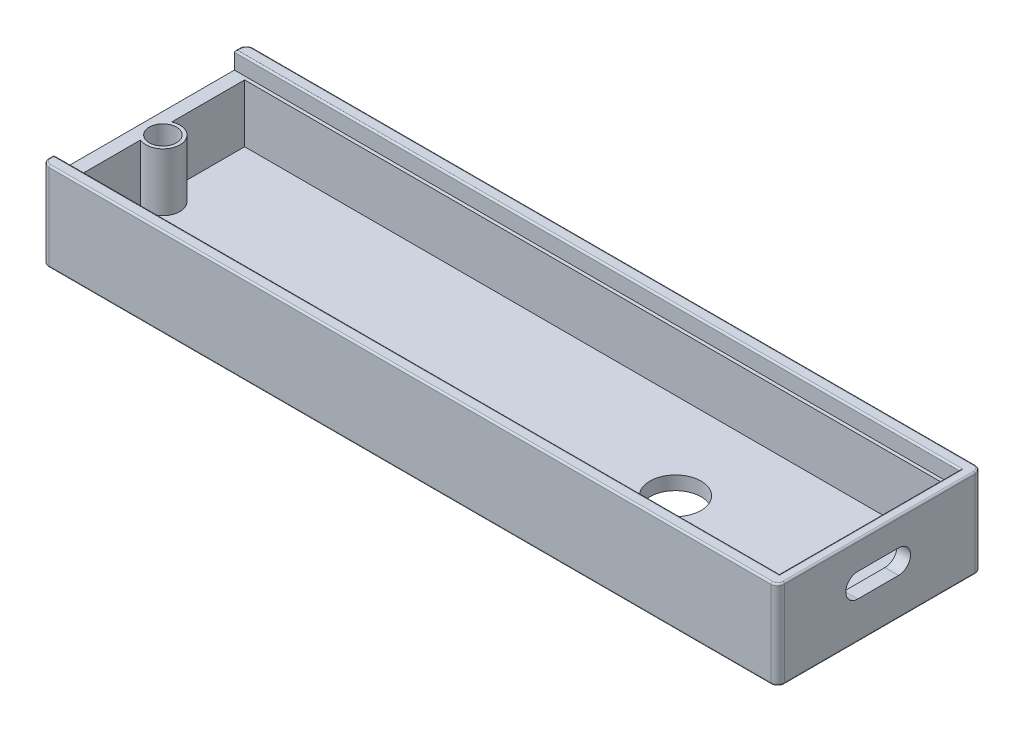
SolidWorks part; units mm, degrees
material "ABS"
ref_plane "Front Plane" through (0, 0, 0) normal (0, 0, 1) x (1, 0, 0)
ref_plane "Top Plane" through (0, 0, 0) normal (0, 1, 0) x (1, 0, 0)
ref_plane "Right Plane" through (0, 0, 0) normal (1, 0, 0) x (0, 0, -1)
sketch "Sketch1" plane through (0, 0, 0) normal (0, 1, 0) x (1, 0, 0)
  line L1 (0, 0) -> (108, 0)
  line L2 (0, 0) -> (0, -30)
  line L3 (0, -30) -> (108, -30)
  line L4 (108, 0) -> (108, -30)
  dimension "D1" = 108
  dimension "D2" = 30
extrude "Boss-Extrude1" add sketch "Sketch1" against normal blind 13
sketch "Sketch2" plane through (0, 0, 0) normal (0, 1, 0) x (1, 0, 0)
  line L0 (0, -30) -> (108, -30) construction
  line L1 (0, -1.75) -> (106.5, -1.75)
  line L2 (0, -1.75) -> (0, -28.25)
  line L3 (0, -28.25) -> (106.5, -28.25)
  line L4 (106.5, -1.75) -> (106.5, -28.25)
  line L6 (108, -30) -> (108, 0) construction
  line L8 (0, 0) -> (0, -30) construction
  line L10 (108, 0) -> (0, 0) construction
  dimension "D1" = 1.75
  dimension "D2" = 1.75
  dimension "D3" = 1.5
extrude "Cut-Extrude1" cut sketch "Sketch2" against normal blind 2.5
sketch "Sketch3" plane through (0, 0, 0) normal (0, 1, 0) x (1, 0, 0)
  line L0 (106.5, -1.75) -> (0, -1.75) construction
  line L1 (2, -2.25) -> (106, -2.25)
  line L2 (2, -2.25) -> (2, -27.75)
  line L3 (2, -27.75) -> (106, -27.75)
  line L4 (106, -2.25) -> (106, -27.75)
  line L5 (106.5, -28.25) -> (106.5, -1.75) construction
  line L6 (0, -28.25) -> (106.5, -28.25) construction
  line L7 (0, -1.75) -> (0, -28.25) construction
  dimension "D1" = 0.5
  dimension "D2" = 0.5
  dimension "D3" = 0.5
  dimension "D4" = 2
extrude "Cut-Extrude2" cut sketch "Sketch3" against normal blind 11
fillet "Fillet1" radius 0.25 12 edges at (0, 0, 0.875) (54, 0, 0) (108, 0, 15) (54, 0, 30) (0, 0, 29.125) (53.25, 0, 28.25) (106.5, 0, 15) (53.25, 0, 1.75) (54, -13, 30) (108, -13, 15) (54, -13, 0) (0, -13, 15)
fillet "Fillet2" radius 1 12 edges at (107.9268, -0.0732, 29.9268) (107.9268, -0.0732, 0.0732) (0.0732, -0.0732, 0.0732) (0.0732, -0.0732, 29.9268) (0, -6.5, 30) (0, -6.5, 0) (108, -6.5, 0) (108, -6.5, 30) (107.9268, -12.9268, 29.9268) (107.9268, -12.9268, 0.0732) (0.0732, -12.9268, 0.0732) (0.0732, -12.9268, 29.9268)
sketch "Sketch4" plane through (0, -11, 0) normal (0, 1, 0) x (1, 0, 0)
  line L0 (0, -1.75) -> (0, -28.25) construction
  line L2 (0, -28.25) -> (106.5, -28.25) construction
  circle A0 centre (3, -15.25) radius 2.5
  dimension "D1" = 5
  dimension "D2" = 3
  dimension "D3" = 13
extrude "Boss-Extrude2" add sketch "Sketch4" along normal up to surface (8.5 mm away) up to face at (54, -2.5, 15)
hole_wizard "Ø2.2 (2.2) Diameter Hole1" positions "3DSketch1" profile "Sketch5" hole size "Ø2.2" standard "ISO"
sketch3d "3DSketch1"
  line L0 (0, -2.5, 1.75) -> (0, -2.5, 28.25) construction
  point P0 (3, -2.5, 15.25)
  dimension "D1" = 3
  dimension "D2" = 13.5
sketch "Sketch5" plane through (3, -2.5, 15.25) normal (1, 0, 0) x (0, 0, 1)
  line L0 (0, 0) -> (0, 7.6609)
  line L1 (0, 7.6609) -> (1.1, 7)
  line L2 (1.1, 7) -> (1.1, 0)
  line L5 (1.1, 0) -> (0, 0)
  line L10 (0, 7.6609) -> (-1.1, 7) construction
  line L11 (0, -6.35) -> (0, 107.95) construction
  dimension "Hole Dia." = 2.2
  dimension "Hole Depth" = 7
  dimension "Drill Angle" = 118
thread "Thread1" pitch 0.4 method cut profile "Thread Profile1" start angle 0, offset 0, length 4, pitch 0.4, diameter 2.2
ref_plane "Plane4" through (1.9, -2.5, 15.25) normal (0, 0, 1) x (-1, 0, 0)
sketch "Thread Profile1" plane through (1.9, -2.5, 15.25) normal (0, 0, 1) x (-1, 0, 0)
  line L0 (0, 0) -> (0, 0.4) construction
  line L1 (0, 0) -> (0.2165, 0.125)
  line L2 (0.2165, 0.125) -> (0.2165, 0.175)
  line L3 (0.2165, 0.175) -> (0, 0.3)
  line L4 (0.2165, 0.15) -> (0, 0.15) construction
  line L11 (0, 0) -> (0, 0.3)
  point P2 (0, 0)
  dimension "Pitch" = 0.4
  dimension "Profile_Angle" = 60
  dimension "Profile_Land" = 0.05
  dimension "Profile_Height" = 0.2165
sketch "Sketch9" plane through (108, 0, 0) normal (1, 0, 0) x (0, 0, -1)
  line L0 (-18.25, -5.75) -> (-12.25, -5.75) construction
  line L1 (-18.25, -4) -> (-12.25, -4)
  line L2 (-18.25, -7.5) -> (-12.25, -7.5)
  line L5 (-30, -12.75) -> (-30, -0.25) construction
  line L6 (-29, -12.75) -> (-1, -12.75) construction
  arc A0 (-18.25, -4) -> (-18.25, -7.5) centre (-18.25, -5.75) ccw
  arc A1 (-12.25, -7.5) -> (-12.25, -4) centre (-12.25, -5.75) ccw
  point P2 (-15.25, -5.75)
  dimension "D1" = 6
  dimension "D2" = 7
  dimension "D3" = 3.5
  dimension "D4" = 14.75
extrude "Cut-Extrude3" cut sketch "Sketch9" against normal up to next
sketch "Sketch10" plane through (0, -13, 0) normal (0, -1, 0) x (1, 0, 0)
  line L0 (107, 29.75) -> (1, 29.75) construction
  line L1 (0.25, 29) -> (0.25, 1) construction
  line L2 (0.25, 14.75) -> (107.75, 14.75) construction
  line L4 (54, 29.25) -> (54, 0) construction
  circle A0 centre (3.25, 26.75) radius 0.75
  circle A1 centre (3.25, 2.75) radius 0.75
  circle A2 centre (104.75, 2.75) radius 0.75
  circle A3 centre (104.75, 26.75) radius 0.75
  dimension "D3" = 1.5
  dimension "D1" = 3
  dimension "D2" = 3
sketch "Sketch11" plane through (106.5, 0, 0) normal (-1, 0, 0) x (0, 0, 1)
  line L0 (28.25, -2.5) -> (28.25, -0.25) construction
  line L1 (1.75, -2.5) -> (28.25, -2.5)
  line L2 (1.75, -2.5) -> (1.75, -1.375)
  line L3 (1.75, -1.375) -> (28.25, -1.375)
  line L4 (28.25, -2.5) -> (28.25, -1.375)
extrude "Cut-Extrude4" cut sketch "Sketch11" against normal blind 1
sketch "Sketch13" plane through (0, -11, 0) normal (0, 1, 0) x (1, 0, 0)
  line L0 (106, -27.75) -> (106, -2.25) construction
  line L2 (1, -30) -> (107, -30) construction
  circle A0 centre (78, -15) radius 3.75
  dimension "D1" = 7.5
  dimension "D2" = 28
  dimension "D3" = 15
extrude "Cut-Extrude5" cut sketch "Sketch13" against normal through all
ref_plane "Plane5" through (0, -12, 0) normal (0, 1, 0) x (1, 0, 0)
sketch "Sketch15" plane through (0, -12, 0) normal (0, 1, 0) x (1, 0, 0)
  circle A0 centre (78, -15) radius 3.5
  dimension "D1" = 7
sketch "Sketch17" plane through (0, -12, 0) normal (0, 1, 0) x (1, 0, 0)
  circle A0 centre (78, -15) radius 4.5
  dimension "D1" = 9
sketch "Sketch18" plane through (0, -2.5, 0) normal (0, 1, 0) x (1, 0, 0)
  circle A0 centre (3, -15.25) radius 2
  dimension "D1" = 4
extrude "Cut-Extrude7" cut sketch "Sketch18" against normal blind 4
